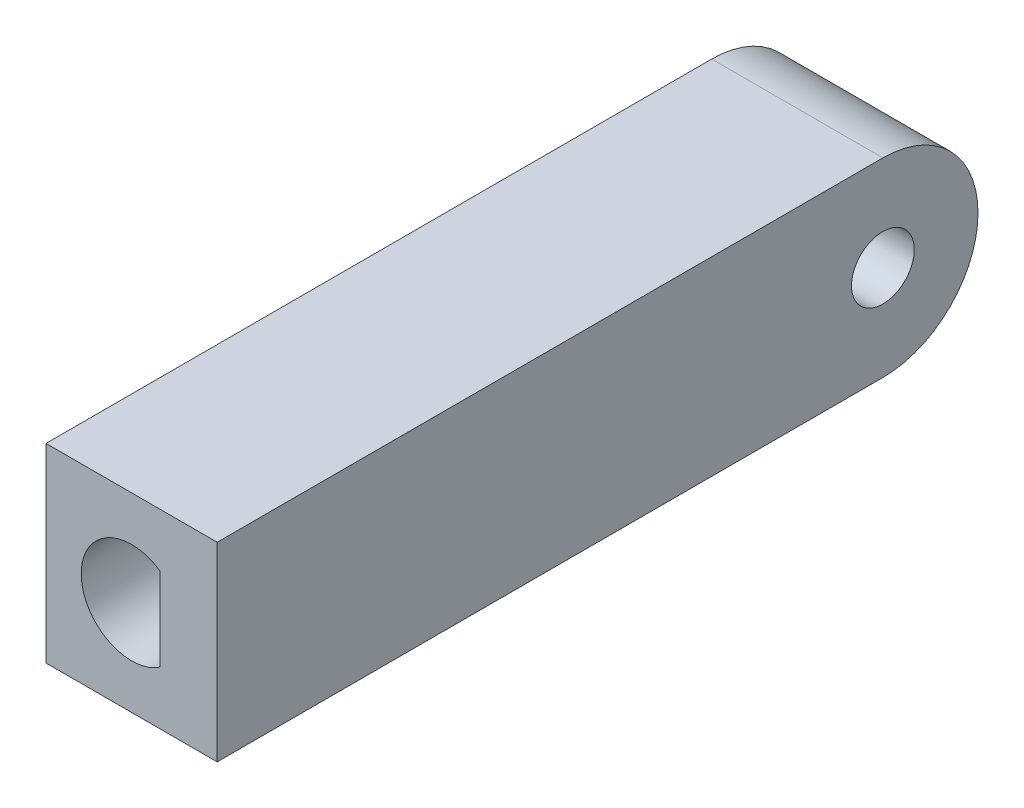
SolidWorks part; units mm, degrees
ref_plane "Ebene vorne" through (0, 0, 0) normal (0, 0, 1) x (1, 0, 0)
ref_plane "Ebene oben" through (0, 0, 0) normal (0, 1, 0) x (1, 0, 0)
ref_plane "Ebene rechts" through (0, 0, 0) normal (1, 0, 0) x (0, 0, -1)
sketch "Skizze1" plane through (0, 0, 0) normal (0, 0, 1) x (1, 0, 0)
  line L1 (0, 0) -> (9, 0)
  line L2 (0, 0) -> (0, 10)
  line L3 (0, 10) -> (9, 10)
  line L4 (9, 0) -> (9, 10)
extrude "Aufsatz-Linear austragen1" add sketch "Skizze1" along normal blind 40
sketch "Skizze3" plane through (0, 0, 0) normal (-1, 0, 0) x (0, 0, 1)
  line L0 (40, 10) -> (0, 10) construction
  line L1 (0, 10) -> (0, 0) construction
  circle A0 centre (5, 5) radius 1.65
  dimension "D2" = 3.3
  dimension "D1" = 5
  dimension "D3" = 5
extrude "Schnitt-Linear austragen2" cut sketch "Skizze3" against normal through all contours A0
fillet "Verrundung1" radius 5 2 edges at (4.5, 0, 0) (4.5, 10, 0)
sketch "Skizze4" plane through (0, 0, 40) normal (0, 0, 1) x (1, 0, 0)
  line L0 (9, 5) -> (0, 5) construction
  line L1 (9, 0) -> (9, 10) construction
  line L2 (0, 10) -> (0, 0) construction
  line L3 (4.5, 10) -> (4.5, 0) construction
  line L4 (9, 10) -> (0, 10) construction
  line L5 (0, 0) -> (9, 0) construction
  line L6 (6, 7.1846) -> (6, 2.8154)
  circle A0 centre (4.5, 5) radius 2.65
  dimension "D1" = 5.3
  dimension "D2" = 1.5
extrude "Schnitt-Linear austragen3" cut sketch "Skizze4" against normal blind 10 contours L6 A0 region at (4.125, 5, 40)
